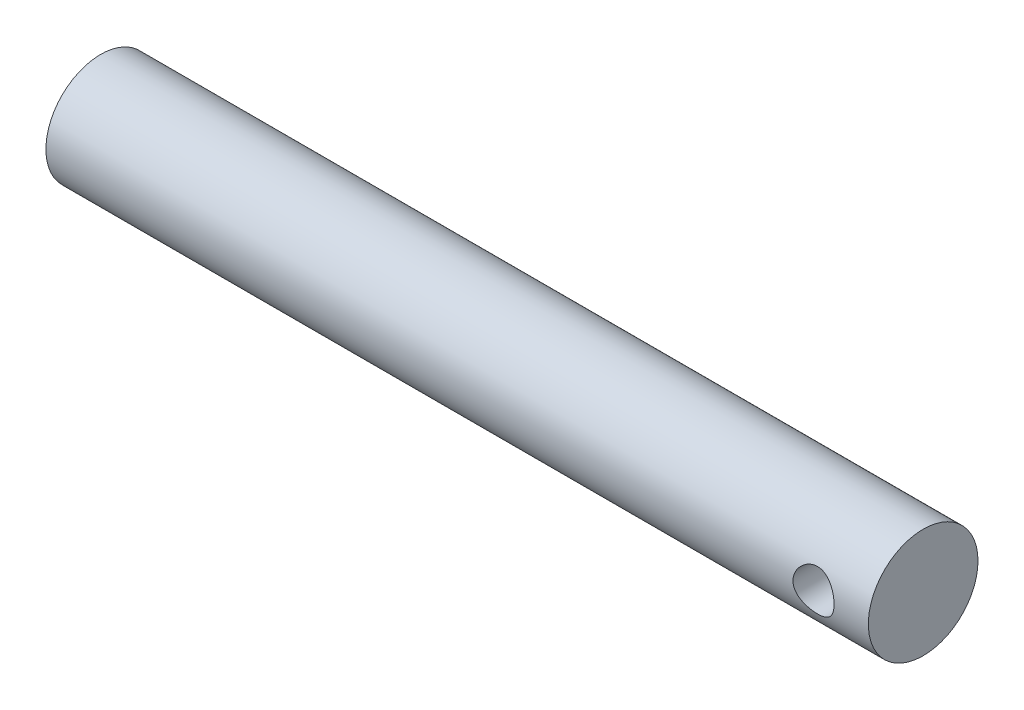
SolidWorks part; units mm, degrees
material "AISI 1010 Steel, hot rolled bar"
ref_plane "front" through (0, 0, 0) normal (0, 0, 1) x (1, 0, 0)
ref_plane "top" through (0, 0, 0) normal (0, 1, 0) x (1, 0, 0)
ref_plane "side" through (0, 0, 0) normal (1, 0, 0) x (0, 0, -1)
sketch "Sketch1" plane through (0, 0, 0) normal (1, 0, 0) x (0, 0, -1)
  circle A0 centre (0, 0) radius 6.35
  dimension "D1" = 12.7
extrude "Base-Extrude" add sketch "Sketch1" along normal blind 95.25
sketch "Sketch2" plane through (0, 0, 0) normal (0, 0, 1) x (1, 0, 0)
  line L0 (95.25, 6.35) -> (95.25, -6.35) construction
  line L1 (50, 0) -> (-50, 0) construction
  circle A0 centre (88.9, 0) radius 2.3813
  dimension "D2" = 4.7625
  dimension "D1" = 6.35
extrude "Cut-Extrude1" cut sketch "Sketch2" against normal through all and the other way through all
ref_axis "Axis1" through (99.738, 0, 0) along (-1, 0, 0)
